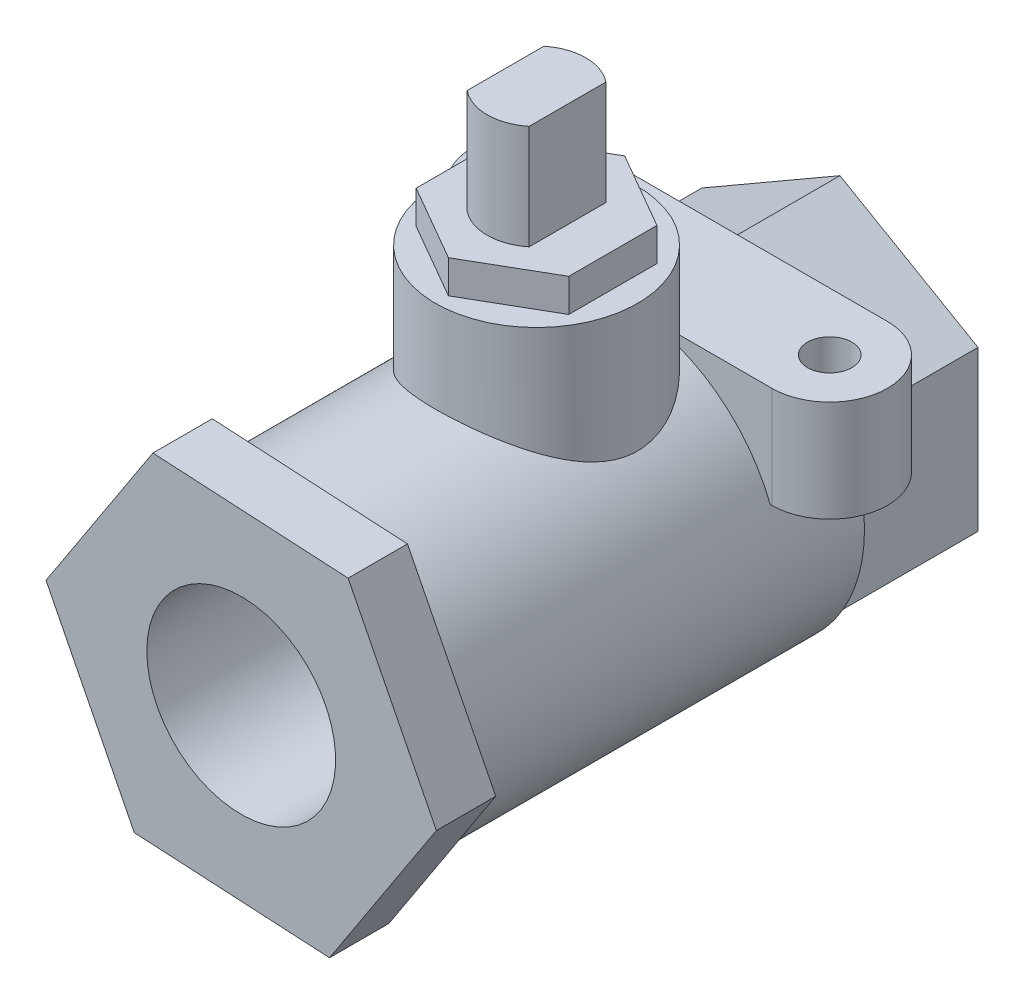
SolidWorks part; units mm, degrees
material "Cast Stainless Steel"
ref_plane "Front Plane" through (0, 0, 0) normal (0, 0, 1) x (1, 0, 0)
ref_plane "Top Plane" through (0, 0, 0) normal (0, 1, 0) x (1, 0, 0)
ref_plane "Right Plane" through (0, 0, 0) normal (1, 0, 0) x (0, 0, -1)
sketch "Sketch1" plane through (0, 0, 0) normal (0, 0, 1) x (1, 0, 0)
  circle A0 centre (0, 0) radius 15.0114
  dimension "D1" = 30.0228
extrude "Boss-Extrude1" add sketch "Sketch1" along normal blind 38.1
sketch "Sketch2" plane through (0, 0, 38.1) normal (0, 0, 1) x (1, 0, 0)
  line L1 (-8.3145, 16.4272) -> (-18.3836, 1.0131)
  line L2 (-18.3836, 1.0131) -> (-10.0691, -15.4142)
  line L3 (-10.0691, -15.4142) -> (8.3145, -16.4272)
  line L4 (8.3145, -16.4272) -> (18.3836, -1.0131)
  line L5 (18.3836, -1.0131) -> (10.0691, 15.4142)
  line L6 (10.0691, 15.4142) -> (-8.3145, 16.4272)
  circle A0 centre (0, 0) radius 15.9448 construction
  point P1 (10.0691, 15.4142)
  dimension "D1" = 31.8897
extrude "Boss-Extrude2" add sketch "Sketch2" along normal blind 5.588
sketch "Sketch3" plane through (0, 0, 0) normal (0, 0, -1) x (-1, 0, 0)
  line L1 (0, 15.0114) -> (-13.0003, 7.5057)
  line L2 (-13.0003, 7.5057) -> (-13.0003, -7.5057)
  line L3 (-13.0003, -7.5057) -> (0, -15.0114)
  line L4 (0, -15.0114) -> (13.0003, -7.5057)
  line L5 (13.0003, -7.5057) -> (13.0003, 7.5057)
  line L6 (13.0003, 7.5057) -> (0, 15.0114)
  circle A0 centre (0, 0) radius 13.0003 construction
  circle A1 centre (0, 0) radius 15.0114 construction
  point P1 (12.9063, 5.0855)
  point P10 (0, 0)
  point P13 (0, 0)
extrude "Boss-Extrude3" add sketch "Sketch3" along normal blind 12.7
ref_plane "Plane1" through (0, 15.0114, 0) normal (0, 1, 0) x (1, 0, 0)
sketch "Sketch5" plane through (0, 15.0114, 0) normal (0, 1, 0) x (1, 0, 0)
  line L0 (-14.1351, -2.4003) -> (14.1351, -2.4003) construction
  line L1 (-14.1351, 3.048) -> (14.1351, 3.048)
  line L2 (-14.1351, -7.8486) -> (14.1351, -7.8486)
  line L3 (-13.0003, 12.7) -> (0, 12.7) construction
  arc A0 (-14.1351, 3.048) -> (-14.1351, -7.8486) centre (-14.1351, -2.4003) ccw
  arc A1 (14.1351, -7.8486) -> (14.1351, 3.048) centre (14.1351, -2.4003) ccw
  point P2 (0, -2.4003)
  point P9 (0, 0)
  dimension "D3" = 28.2702
  dimension "D1" = 9.652
  dimension "D2" = 10.8966
extrude "Boss-Extrude4" add sketch "Sketch5" against normal blind 9.5504
sketch "Sketch4" plane through (0, 0, -12.7) normal (0, 0, -1) x (-1, 0, 0)
  circle A0 centre (0, 0) radius 8.89
  dimension "D1" = 17.78
extrude "Cut-Extrude1" cut sketch "Sketch4" against normal through all
sketch "Sketch6" plane through (0, 15.0114, 0) normal (0, 1, 0) x (1, 0, 0)
  line L0 (0, 12.7) -> (13.0003, 12.7) construction
  circle A0 centre (0, -15.875) radius 9.525
  point P2 (0, -20.3655)
  point P3 (4.2518, -19.7114)
  point P4 (0, 0)
  point P6 (0, -16.2954)
  dimension "D1" = 19.05
  dimension "D2" = 28.575
extrude "Boss-Extrude5" add sketch "Sketch6" along normal blind 8.636 and the other way blind 5.08
sketch "Sketch7" plane through (0, 23.6474, 0) normal (0, 1, 0) x (1, 0, 0)
  line L1 (0, -7.5748) -> (-7.1882, -11.7249)
  line L2 (-7.1882, -11.7249) -> (-7.1882, -20.0251)
  line L3 (-7.1882, -20.0251) -> (0, -24.1752)
  line L4 (0, -24.1752) -> (7.1882, -20.0251)
  line L5 (7.1882, -20.0251) -> (7.1882, -11.7249)
  line L6 (7.1882, -11.7249) -> (0, -7.5748)
  circle A0 centre (0, -15.875) radius 7.1882 construction
  point P1 (0, 0)
  dimension "D1" = 14.3764
extrude "Boss-Extrude6" add sketch "Sketch7" along normal blind 3.1115
sketch "Sketch8" plane through (0, 26.7589, 0) normal (0, 1, 0) x (1, 0, 0)
  line L1 (-2.921, -19.4907) -> (2.921, -19.4907)
  line L2 (-2.921, -19.4907) -> (-2.921, -12.2593)
  line L3 (-2.921, -12.2593) -> (2.921, -12.2593)
  line L4 (2.921, -19.4907) -> (2.921, -12.2593)
  line L5 (-2.921, -19.4907) -> (2.921, -12.2593) construction
  line L6 (-2.921, -12.2593) -> (2.921, -19.4907) construction
  circle A0 centre (0, -15.875) radius 4.6482
  circle A1 centre (0, -15.875) radius 9.525
  circle A2 centre (0, -15.875) radius 9.525 construction
  dimension "D3" = 9.2964
  dimension "D2" = 5.842
  dimension "D1" = 0
extrude "Boss-Extrude7" add sketch "Sketch8" along normal blind 9.8298 contours L1 L4 L3 L2 | L3 A0 | L1 A0 region at (0, 26.7589, 15.875) region at (0, 26.7589, 19.9079) region at (0, 26.7589, 11.8421)
sketch "Sketch9" plane through (0, 15.0114, 0) normal (0, 1, 0) x (1, 0, 0)
  line L4 (5.1286, -7.8486) -> (14.1351, -7.8486)
  line L5 (14.1351, 3.048) -> (0, 3.048)
  line L6 (0, 3.048) -> (-14.1351, 3.048)
  line L7 (-14.1351, -7.8486) -> (-5.1286, -7.8486)
  line L8 (5.1286, -7.8486) -> (14.1351, -7.8486)
  line L9 (14.1351, 3.048) -> (0, 3.048)
  line L10 (0, 3.048) -> (-14.1351, 3.048)
  line L11 (-14.1351, -7.8486) -> (-5.1286, -7.8486)
  circle A0 centre (-14.1351, -2.4003) radius 2.0892
  circle A1 centre (14.1351, -2.4003) radius 2.0891
  arc A3 (5.1286, -7.8486) -> (-5.1286, -7.8486) centre (0, -15.875) ccw
  arc A4 (14.1351, -7.8486) -> (14.1351, 3.048) centre (14.1351, -2.4003) ccw
  arc A5 (-14.1351, 3.048) -> (-14.1351, -7.8486) centre (-14.1351, -2.4003) ccw
  arc A6 (5.1286, -7.8486) -> (-5.1286, -7.8486) centre (0, -15.875) ccw
  arc A7 (14.1351, -7.8486) -> (14.1351, 3.048) centre (14.1351, -2.4003) ccw
  arc A8 (-14.1351, 3.048) -> (-14.1351, -7.8486) centre (-14.1351, -2.4003) ccw
  dimension "D2" = 4.1783
  dimension "D1" = 0
extrude "Cut-Extrude2" cut sketch "Sketch9" against normal blind 8.89 contours A1 | A0 region at (-14.1351, 15.0114, 2.4003) region at (14.1351, 15.0114, 2.4003)
